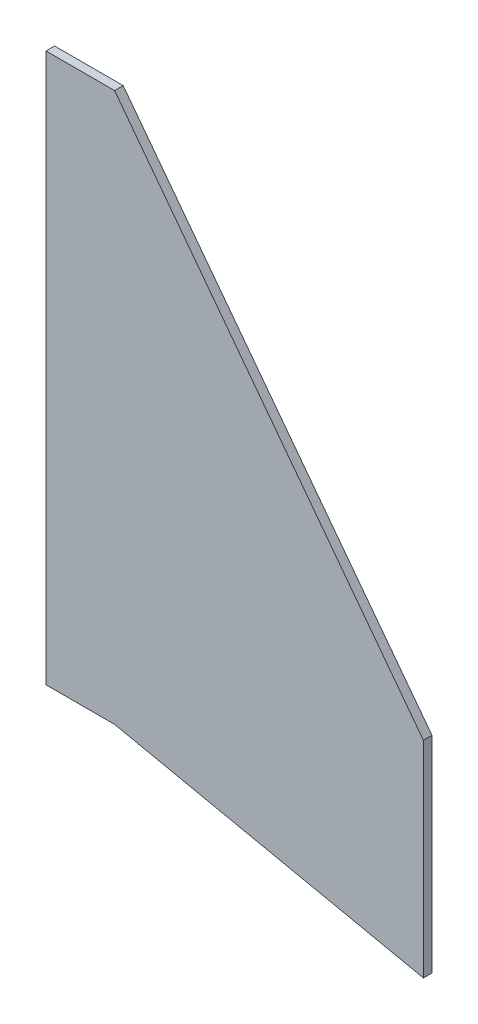
SolidWorks part; units mm, degrees
ref_plane "Front Plane" through (0, 0, 0) normal (0, 0, 1) x (1, 0, 0)
ref_plane "Top Plane" through (0, 0, 0) normal (0, 1, 0) x (1, 0, 0)
ref_plane "Right Plane" through (0, 0, 0) normal (1, 0, 0) x (0, 0, -1)
sketch "Sketch1" plane through (0, 0, 0) normal (0, 0, 1) x (1, 0, 0)
  line L0 (0, 0) -> (0, -203.2)
  line L1 (0, -203.2) -> (114.3, -227.3317)
  line L2 (114.3, -227.3317) -> (114.3, -151.1317)
  line L3 (114.3, -151.1317) -> (0, 0)
  line L4 (0, 0) -> (-25.4, 0)
  line L5 (-25.4, 0) -> (-25.4, -203.2)
  line L6 (-25.4, -203.2) -> (0, -203.2)
  line L7 (0, 0) -> (114.3, 0) construction
  dimension "D1" = 203.2
  dimension "D2" = 76.2
  dimension "D3" = 114.3
  dimension "D4" = 52.9
  dimension "D5" = 25.4
extrude "Boss-Extrude1" add sketch "Sketch1" along normal mid plane 3.175 contours L5 L6 L0 L4 | L2 L3 L0 L1 region at (48.4909, -138.7771, 0) region at (-12.7, -101.6, 0)
